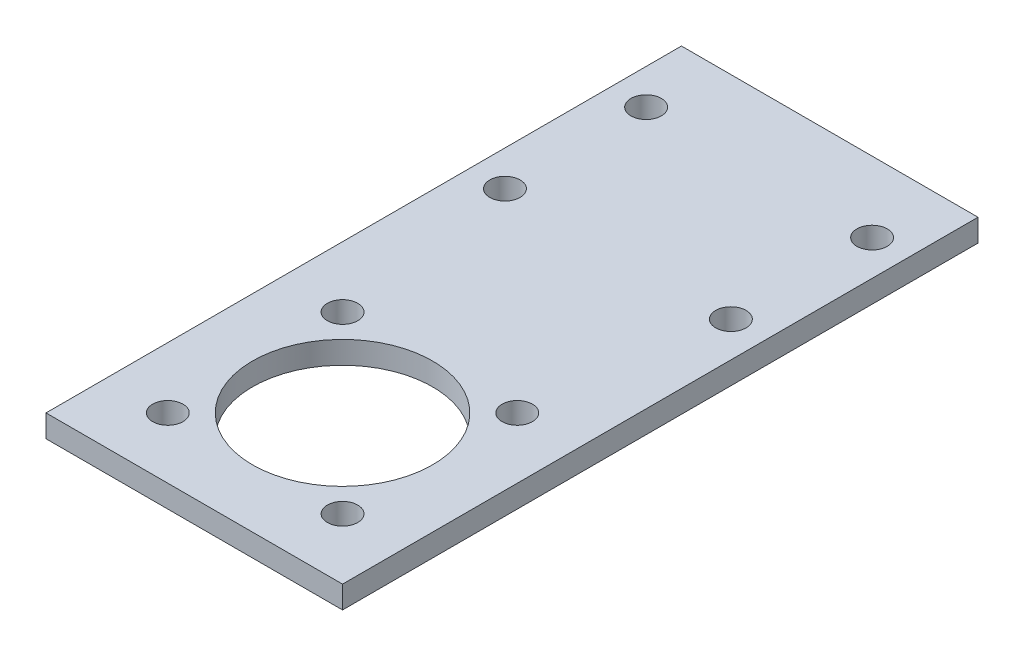
SolidWorks part; units mm, degrees
material "6061 Alloy"
ref_plane "Front Plane" through (0, 0, 0) normal (0, 0, 1) x (1, 0, 0)
ref_plane "Top Plane" through (0, 0, 0) normal (0, 1, 0) x (1, 0, 0)
ref_plane "Right Plane" through (0, 0, 0) normal (1, 0, 0) x (0, 0, -1)
sketch "Sketch1" plane through (0, 0, 0) normal (0, 1, 0) x (1, 0, 0)
  line L1 (0, 0) -> (42, 0)
  line L2 (0, 0) -> (0, 90)
  line L3 (0, 90) -> (42, 90)
  line L4 (42, 0) -> (42, 90)
  circle A0 centre (21, 21) radius 12.75
  point P5 (21, 21)
  dimension "D5" = 25.5
  dimension "D1" = 42
  dimension "D2" = 90
  dimension "D3" = 21
  dimension "D4" = 21
extrude "Boss-Extrude1" add sketch "Sketch1" along normal blind 3.175
sketch "Sketch2" plane through (0, 3.175, 0) normal (0, 1, 0) x (1, 0, 0)
  line L0 (42, 90) -> (0, 90) construction
  line L1 (0, 90) -> (0, 0) construction
  point P0 (8.6256, 33.3744)
  point P1 (21, 21)
  point P4 (5, 80)
  point P6 (33.3744, 33.3744)
  point P7 (33.3744, 8.6256)
  point P8 (8.6256, 8.6256)
  point P14 (37, 80)
  point P15 (37, 60)
  point P16 (5, 60)
  dimension "D1" = 17.5
  dimension "D3" = 10
  dimension "D4" = 5
  dimension "D7" = 20
  dimension "D8" = 32
  dimension "D5" = 2
  dimension "D6" = 2
  dimension "D2" = 4
hole_wizard "M4 Clearance Hole1" positions "Sketch2" profile "Sketch4" hole size "M4" standard "ANSI Metric" end condition through all
sketch "Sketch4" plane through (8.6256, 3.175, -33.3744) normal (1, 0, 0) x (0, 0, 1)
  line L0 (0, 0) -> (0, 3.175)
  line L1 (0, 3.175) -> (2.15, 3.175)
  line L2 (2.15, 3.175) -> (2.15, 0)
  line L5 (2.15, 0) -> (0, 0)
  line L11 (0, -6.35) -> (0, 107.95) construction
  dimension "Thru Hole Dia." = 4.3
  dimension "Thru Hole Depth" = 3.175
sketch "Sketch5" plane through (0, 3.175, 0) normal (0, 1, 0) x (1, 0, 0)
  line L0 (21, 21) -> (-60.1544, 70) construction
  line L1 (5, 80) -> (5, 60) construction
  line L2 (5, 70) -> (-60.1544, 70) construction
  dimension "D1" = 94.8
ref_axis "Axis1" through (-60.1544, -81.192, -70) along (0, 1, 0)
